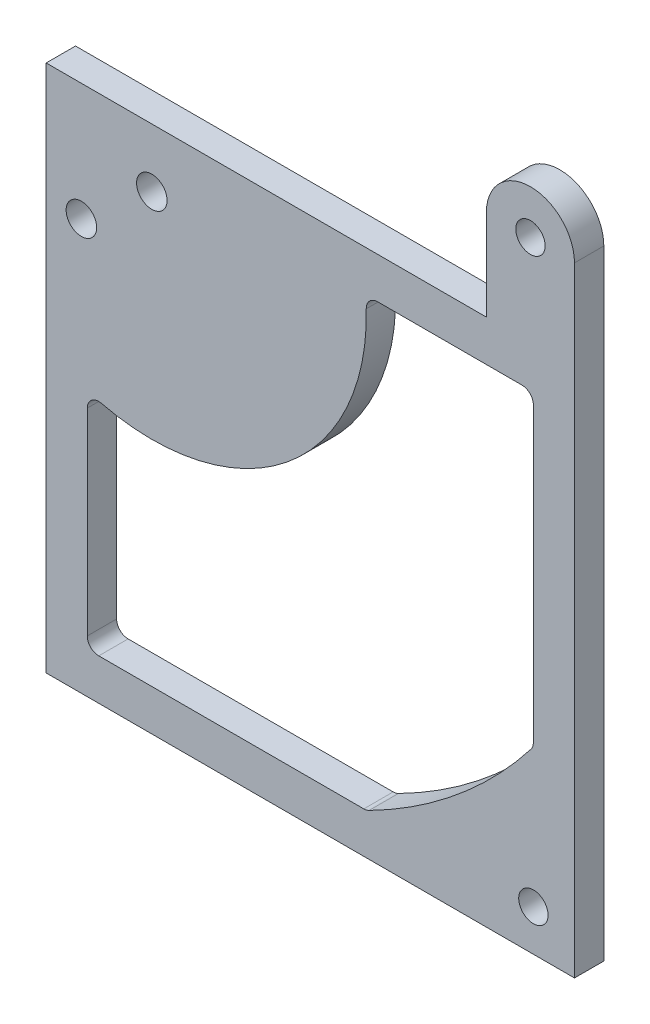
SolidWorks part; units mm, degrees
ref_plane "Front Plane" through (0, 0, 0) normal (0, 0, 1) x (1, 0, 0)
ref_plane "Top Plane" through (0, 0, 0) normal (0, 1, 0) x (1, 0, 0)
ref_plane "Right Plane" through (0, 0, 0) normal (1, 0, 0) x (0, 0, -1)
sketch "Sketch1" plane through (0, 0, 0) normal (0, 0, 1) x (1, 0, 0)
  line L1 (-57.15, -57.15) -> (57.15, -57.15)
  line L2 (-57.15, -57.15) -> (-57.15, 57.15)
  line L3 (-57.15, 57.15) -> (38.1, 57.15)
  line L4 (57.15, -57.15) -> (57.15, 76.835)
  line L5 (57.15, -57.15) -> (-57.15, 57.15) construction
  line L19 (47.625, 76.835) -> (47.625, 48.26) construction
  line L22 (38.1, 76.835) -> (38.1, 57.15)
  line L24 (-45.7715, -48.2506) -> (11.5718, -48.2506)
  line L25 (-48.26, -45.7621) -> (-48.26, -3.0766)
  line L27 (48.26, -17.4506) -> (48.26, 45.7715)
  line L30 (14.5859, 48.26) -> (45.7715, 48.26)
  line L31 (48.26, -17.4506) -> (48.26, -48.2506) construction
  line L32 (11.5718, -48.2506) -> (48.26, -48.2506) construction
  circle A17 centre (-49.53, 31.75) radius 3.302
  circle A18 centre (-34.29, 44.45) radius 3.302
  arc A34 (-45.1872, -0.6577) -> (12.0984, 45.7043) centre (-34.29, 44.45) ccw
  arc A36 (12.6995, -47.9804) -> (47.7402, -18.9727) centre (-34.29, 44.45) ccw
  arc A37 (-45.1872, -0.6577) -> (-48.26, -3.0766) centre (-45.7715, -3.0766) ccw
  arc A38 (-45.7715, -48.2506) -> (-48.26, -45.7621) centre (-45.7715, -45.7621) cw
  arc A39 (12.6995, -47.9804) -> (11.5718, -48.2506) centre (11.5718, -45.7621) cw
  arc A40 (48.26, -17.4506) -> (47.7402, -18.9727) centre (45.7715, -17.4506) cw
  arc A41 (45.7715, 48.26) -> (48.26, 45.7715) centre (45.7715, 45.7715) cw
  arc A42 (12.0984, 45.7043) -> (14.5859, 48.26) centre (14.5859, 45.7715) cw
  circle A44 centre (48.26, -48.2506) radius 3.175
  circle A45 centre (47.625, 76.835) radius 3.175
  arc A46 (38.1, 76.835) -> (57.15, 76.835) centre (47.625, 76.835) cw
  point P0 (0, 0)
  point P16 (0, 0)
  dimension "D4" = 6.604
  dimension "D5" = 6.35
  dimension "D6" = 8.89
  dimension "D9" = 6.604
  dimension "D11" = 114.3
  dimension "D12" = 6.35
  dimension "D16" = 114.3
  dimension "D10" = 6.35
  dimension "D17" = 103.6889
  dimension "D18" = 46.4053
  dimension "D1" = 7.62
  dimension "D2" = 8.89
  dimension "D3" = 25.4
  dimension "D7" = 22.86
  dimension "D8" = 12.7
  dimension "D14" = 8.8994
  dimension "D15" = 8.89
  dimension "D19" = 28.575
extrude "Boss-Extrude1" add sketch "Sketch1" along normal mid plane 6.35
